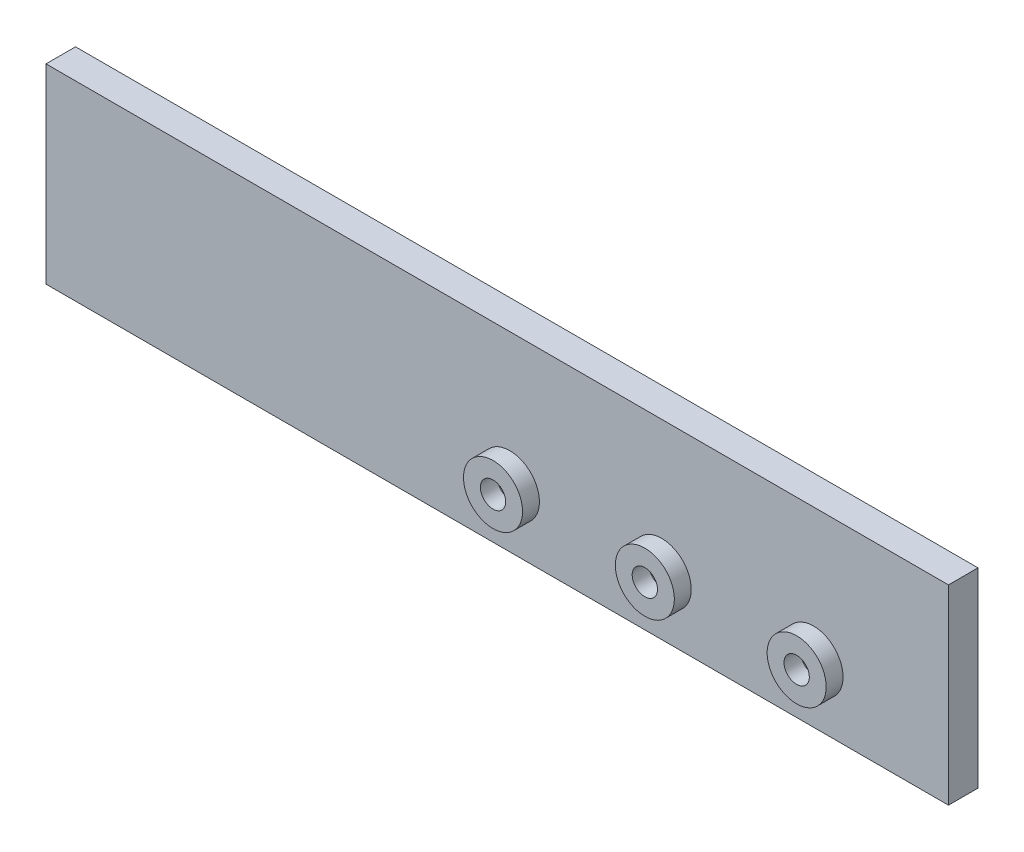
SolidWorks part; units mm, degrees
ref_plane "Plano frontal" through (0, 0, 0) normal (0, 0, 1) x (1, 0, 0)
ref_plane "Plano superior" through (0, 0, 0) normal (0, 1, 0) x (1, 0, 0)
ref_plane "Plano direito" through (0, 0, 0) normal (1, 0, 0) x (0, 0, -1)
sketch "Esboço1" plane through (0, 0, 0) normal (0, 0, 1) x (1, 0, 0)
  line L1 (-40.6777, 33.2717) -> (66.3223, 33.2717)
  line L2 (-40.6777, 33.2717) -> (-40.6777, 10.6517)
  line L3 (-40.6777, 10.6517) -> (66.3223, 10.6517)
  line L4 (66.3223, 33.2717) -> (66.3223, 10.6517)
  circle A0 centre (14.3223, 17.5517) radius 1.5
  circle A1 centre (32.3223, 17.5517) radius 1.5
  circle A2 centre (50.3223, 17.5517) radius 1.5
  circle A3 centre (14.3223, 17.5517) radius 3.5
  circle A4 centre (32.3223, 17.5517) radius 3.5
  circle A5 centre (50.3223, 17.5517) radius 3.5
  point P4 (14.3223, 10.6517)
  point P5 (14.3223, 10.6517)
  point P13 (0, 0)
  point P14 (0, 0)
  dimension "D4" = 3
  dimension "D7" = 7
  dimension "D1" = 107
  dimension "D2" = 22.62
  dimension "D3" = 55
  dimension "D5" = 6.9
  dimension "D6" = 3
  dimension "D9" = 18
  dimension "D10" = 18
  dimension "D8" = 3
extrude "Ressalto-extrusão1" add sketch "Esboço1" along normal blind 3.5 contours L4 L1 L2 L3 A5 A4 A3 | A3 | A4 | A5 region at (11.8455, 22.1826, 0)
extrude "Ressalto-extrusão2" add sketch "Esboço1<4>" along normal blind 5.5 contours A3 | A4 | A5
sketch "Esboço1<4>" plane through (0, 0, 0) normal (0, 0, 1) x (1, 0, 0) same geometry as "Esboço1"
extrude "Corte-extrusão1" cut sketch "Esboço1<7>" along normal blind 5.5 contours A0 | A1 | A2
sketch "Esboço1<7>" plane through (0, 0, 0) normal (0, 0, 1) x (1, 0, 0) same geometry as "Esboço1"
extrude "Ressalto-extrusão4" add sketch "Esboço1<9>" along normal blind 3.5 contours A0 | A1 | A2
sketch "Esboço1<9>" plane through (0, 0, 0) normal (0, 0, 1) x (1, 0, 0) same geometry as "Esboço1"
